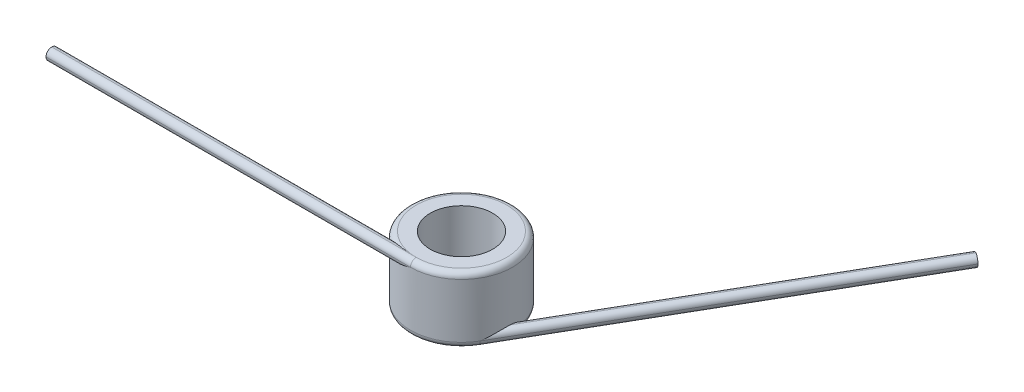
SolidWorks part; units mm, degrees
material "Plain Carbon Steel"
ref_plane "Front Plane" through (0, 0, 0) normal (0, 0, 1) x (1, 0, 0)
ref_plane "Top Plane" through (0, 0, 0) normal (0, 1, 0) x (1, 0, 0)
ref_plane "Right Plane" through (0, 0, 0) normal (1, 0, 0) x (0, 0, -1)
sketch "Sketch2" plane through (0, 0, 0) normal (0, 1, 0) x (1, 0, 0)
  circle A0 centre (0, 0) radius 7.112
  circle A1 centre (0, 0) radius 4.3561
  dimension "D1" = 8.7122
  dimension "D2" = 14.224
extrude "Boss-Extrude1" add sketch "Sketch2" along normal blind 9.1948
sketch "Sketch3" plane through (0, 9.1948, 0) normal (0, 1, 0) x (1, 0, 0)
  line L0 (0, -7.112) -> (-50.8, -7.112)
  line L1 (-50.8, -7.112) -> (-50.8, -5.5118)
  line L2 (-50.8, -5.5118) -> (-4.4945, -5.5118)
  circle A1 centre (0, 0) radius 7.112
  arc A2 (-4.4945, -5.5118) -> (0, -7.112) centre (0, 0) ccw
  dimension "D2" = 1.6002
  dimension "D3" = 50.8
extrude "Boss-Extrude2" add sketch "Sketch3" against normal blind 1.6002
sketch "Sketch4" plane through (0, 0, 0) normal (0, -1, 0) x (1, 0, 0)
  line L0 (6.1592, 3.556) -> (31.5592, -40.4381)
  line L1 (31.5592, -40.4381) -> (30.1734, -41.2382)
  line L2 (30.1734, -41.2382) -> (7.0206, -1.1365)
  line L3 (-4.4945, 5.5118) -> (-50.8, 5.5118) construction
  circle A0 centre (0, 0) radius 7.112 construction
  circle A1 centre (0, 0) radius 7.112
  arc A2 (7.0206, -1.1365) -> (6.1592, 3.556) centre (0, 0) ccw
  dimension "D2" = 1.6002
  dimension "D3" = 50.8
  dimension "D4" = 120
extrude "Boss-Extrude3" add sketch "Sketch4" against normal blind 1.6002
fillet "Fillet1" radius 0.8001 10 edges at (-25.4, 9.1948, 7.112) (18.8592, 0, -18.441) (-25.4, 7.5946, 7.112) (-27.6473, 9.1948, 5.5118) (-27.6473, 7.5946, 5.5118) (2.3854, 9.1948, -6.7) (18.597, 1.6002, -21.1873) (18.8592, 1.6002, -18.441) (-6.9951, 0, -1.2842) (18.597, 0, -21.1873)
equation "\"wire\"= .063"
equation "\"od\"= .56"
equation "\"id\"= .343"
equation "\"leg\"= 2"
equation "\"length\"= .362"
equation "\"D1@Sketch2\"=\"id\""
equation "\"D2@Sketch2\"=\"od\""
equation "\"D1@Boss-Extrude1\"=\"length\""
equation "\"D2@Sketch3\"=\"wire\""
equation "\"D3@Sketch3\"=\"leg\""
equation "\"D1@Boss-Extrude2\"=\"wire\""
equation "\"D2@Sketch4\"=\"wire\""
equation "\"D3@Sketch4\"=\"leg\""
equation "\"D1@Boss-Extrude3\"=\"wire\""
equation "\"D1@Fillet1\"=\"wire\"/2"
